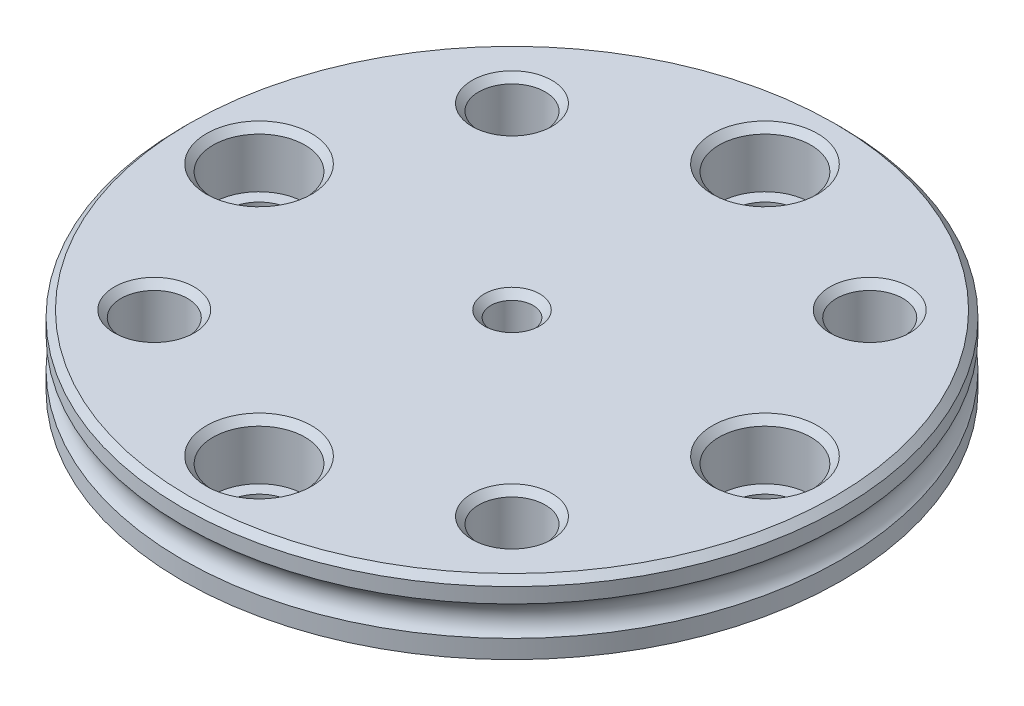
SolidWorks part; units mm, degrees
ref_plane "Front Plane" through (0, 0, 0) normal (0, 0, 1) x (1, 0, 0)
ref_plane "Top Plane" through (0, 0, 0) normal (0, 1, 0) x (1, 0, 0)
ref_plane "Right Plane" through (0, 0, 0) normal (1, 0, 0) x (0, 0, -1)
sketch "Sketch1" plane through (0, 0, 0) normal (0, 1, 0) x (1, 0, 0)
  line L0 (0, 0) -> (0, 19) construction
  circle A1 centre (0, 19) radius 8.5 construction
  circle A2 centre (19, 0) radius 3
  circle A3 centre (19, 0) radius 1.5313
  circle A5 centre (0, 19) radius 10 construction
  circle A10 centre (0, 19) radius 3
  circle A12 centre (0, -19) radius 3
  circle A14 centre (0, 19) radius 1.5313
  circle A17 centre (0, -19) radius 1.5313
  circle A18 centre (-19, 0) radius 3
  circle A19 centre (-19, 0) radius 1.5313
  point P13 (0, 0)
  point P24 (0, 0)
  point P26 (0, 0)
  point P30 (0, 0)
  dimension "D5" = 17
  dimension "D7" = 6
  dimension "D8" = 3.0625
  dimension "D2" = 19
  dimension "D3" = 19
  dimension "D6" = 19
sketch "Sketch2" plane through (0, 0, 0) normal (0, 1, 0) x (-1, 0, 0)
  line L0 (0, 0) -> (-13.435, 13.435) construction
  circle A0 centre (0, 0) radius 23.75
  circle A2 centre (0, 0) radius 19 construction
  circle A3 centre (-13.435, 13.435) radius 2.5
  circle A4 centre (13.435, 13.435) radius 2.5
  circle A8 centre (0, 0) radius 1.5875
  circle A9 centre (13.435, -13.435) radius 2.5
  circle A10 centre (0, 19) radius 2.5
  circle A11 centre (19, 0) radius 2.5
  circle A12 centre (0, -19) radius 2.5
  circle A13 centre (-19, 0) radius 2.5
  circle A14 centre (-13.435, -13.435) radius 2.5
  point P19 (0, 0)
  point P27 (0, 0)
  dimension "D1" = 3.175
  dimension "D2" = 47.5
  dimension "D4" = 5
  dimension "D6" = 5
  dimension "D3" = 4
  dimension "D5" = 4
extrude "Boss-Extrude2" add sketch "Sketch2" against normal blind 5
sketch "Sketch3" plane through (0, 0, 0) normal (0, 1, 0) x (1, 0, 0)
  circle A0 centre (0, 19) radius 3.45
  circle A1 centre (19, 0) radius 3.45
  circle A2 centre (0, -19) radius 3.45
  circle A3 centre (-19, 0) radius 3.45
  point P12 (0, 0)
  dimension "D1" = 6.9
  dimension "D2" = 4
extrude "Cut-Extrude1" cut sketch "Sketch3" against normal blind 4
sketch "Sketch4" plane through (0, 0, 0) normal (0, 0, 1) x (1, 0, 0)
  line L0 (-23.75, -5) -> (-23.75, 0) construction
  line L1 (-23.75, 0) -> (-23.75, -5) construction
  line L2 (-23.75, 0) -> (-24.75, 0) construction
  line L3 (-27.75, 0) -> (-27.75, -5) construction
  line L4 (-27.75, -5) -> (-25.75, -5) construction
  line L5 (-23.75, -5) -> (-24.75, -5) construction
  line L6 (-25.75, -5) -> (-25.75, 0) construction
  line L7 (-25.75, -1.95) -> (-25.75, 0) construction
  line L8 (-24.75, 0) -> (-23.75, 0)
  line L11 (-23.75, -2.5) -> (-17.0406, -2.5) construction
  line L12 (-23.75, -5) -> (-24.75, -5) construction
  line L14 (-24.75, -5) -> (-23.75, -5)
  line L15 (-25.75, -3.05) -> (-25.75, -5) construction
  line L16 (-24.75, 0) -> (-24.75, -1.382)
  line L17 (-24.75, -5) -> (-24.75, -3.618)
  line L18 (-25.75, 0) -> (-27.75, 0) construction
  line L19 (-24.75, -5) -> (-23.75, -5) construction
  line L20 (-25.75, -5) -> (-27.75, -5) construction
  line L21 (-26.75, -5) -> (-26.75, -3.618)
  line L22 (-26.75, 0) -> (-26.75, -1.382)
  line L23 (-26.75, 0) -> (-35, 0)
  line L24 (-35, 0) -> (-35, -5)
  line L25 (-35, -5) -> (-26.75, -5)
  line L26 (23.75, -2.5) -> (-23.75, -2.5) construction
  line L27 (23.75, 0) -> (-23.75, 0) construction
  line L28 (23.75, -5) -> (23.75, 0) construction
  line L29 (0, -2.5) -> (0, 0) construction
  line L30 (-23.75, -2.5) -> (-35, -2.5) construction
  line L31 (-23.75, 0) -> (-23.75, -5)
  arc A5 (-26.75, -1.382) -> (-26.75, -3.618) centre (-25.75, -2.5) ccw
  arc A6 (-24.75, -3.618) -> (-24.75, -1.382) centre (-25.75, -2.5) ccw
  dimension "D1" = 1.5
  dimension "D3" = 1
  dimension "D2" = 2
  dimension "D4" = 35
revolve "Revolve1" add sketch "Sketch4" angle 360 about L29
sketch "Sketch5" plane through (0, 0, 0) normal (0, 1, 0) x (1, 0, 0)
  circle A0 centre (0, 0) radius 32.5 construction
  circle A1 centre (0, 32.5) radius 2
  circle A2 centre (32.5, 0) radius 2
  circle A3 centre (0, -32.5) radius 2
  circle A4 centre (-32.5, 0) radius 2
  point P14 (0, 0)
  dimension "D1" = 4
extrude "Cut-Extrude2" cut sketch "Sketch5" against normal blind 10
sketch "Sketch6" plane through (0, 0, 0) normal (0, 1, 0) x (1, 0, 0)
  circle A0 centre (0, -32.5) radius 4
  circle A1 centre (-32.5, 0) radius 4
  circle A2 centre (0, 32.5) radius 4
  circle A3 centre (32.5, 0) radius 4
  point P12 (0, 0)
  dimension "D1" = 8
extrude "Cut-Extrude3" cut sketch "Sketch6" against normal blind 4
chamfer "Chamfer2" distance 1 angle 45 9 edges at (0, 0, -26.75) (-28.5, 0, 0) (-24.7487, 0, -24.7487) (0, 0, -28.5) (24.7487, 0, -24.7487) (28.5, 0, 0) (24.7487, 0, 24.7487) (0, 0, 28.5) (-24.7487, 0, 24.7487)
sketch "Sketch7" plane through (0, 0, 0) normal (0, 1, 0) x (1, 0, 0)
  circle A0 centre (0, 0) radius 24.75
  circle A1 centre (13.435, 13.435) radius 2.5
  circle A2 centre (13.435, 13.435) radius 2.5
  circle A3 centre (-13.435, 13.435) radius 2.5
  circle A4 centre (-13.435, 13.435) radius 2.5
  circle A5 centre (0, 0) radius 1.5875
  circle A6 centre (0, 0) radius 1.5875
  circle A7 centre (-13.435, -13.435) radius 2.5
  circle A8 centre (-13.435, -13.435) radius 2.5
  circle A9 centre (13.435, -13.435) radius 2.5
  circle A10 centre (13.435, -13.435) radius 2.5
  circle A11 centre (-19, 0) radius 3.45
  circle A12 centre (-19, 0) radius 3.45
  circle A13 centre (0, -19) radius 3.45
  circle A14 centre (0, -19) radius 3.45
  circle A15 centre (19, 0) radius 3.45
  circle A16 centre (19, 0) radius 3.45
  circle A17 centre (0, 19) radius 3.45
  circle A18 centre (0, 19) radius 3.45
  dimension "D1" = 0
  dimension "D2" = 0
  dimension "D3" = 0
  dimension "D4" = 0
  dimension "D5" = 0
  dimension "D6" = 0
  dimension "D7" = 0
  dimension "D8" = 0
  dimension "D9" = 0
extrude "Boss-Extrude3" add sketch "Sketch7" along normal blind 0.25
chamfer "Chamfer3" distance 0.5 angle 45 10 edges at (0, 0.25, -15.55) (0, 0.25, 22.45) (13.435, 0.25, 15.935) (0, 0.25, 1.5875) (13.435, 0.25, -10.935) (0, 0.25, 24.75) (-13.435, 0.25, -10.935) (-13.435, 0.25, 15.935) (-19, 0.25, 3.45) (19, 0.25, 3.45)
sketch "Sketch8" plane through (0, 0, 0) normal (0, 0, 1) x (1, 0, 0)
  line L0 (25.75, -2.5) -> (0, -2.5) construction
  line L3 (-35, -5) -> (35, -5) construction
  line L4 (-26.75, -5) -> (26.75, -5) construction
  line L5 (26.75, -5) -> (24.75, -5) construction
  line L6 (-24.75, -5) -> (24.75, -5) construction
  line L10 (25.75, -1) -> (25.75, -4)
  arc A0 (25.75, -1) -> (25.75, -4) centre (25.75, -2.5) ccw
  dimension "D1" = 25.75
  dimension "D2" = 1.5
  dimension "D3" = 2.5
revolve "Revolve2" add sketch "Sketch8" angle 360 about L10
pattern_circular "CirPattern1" count 12 over 360 about axis through (0, 0, 0) along (0, 1, 0) of bodies 121
delete or keep bodies "Body-Delete/Keep 1" bodies 122 123 124 125 126 127 128 129 130 131 132
delete or keep bodies "Body-Delete/Keep 2" type delete bodies bodies 121 118
